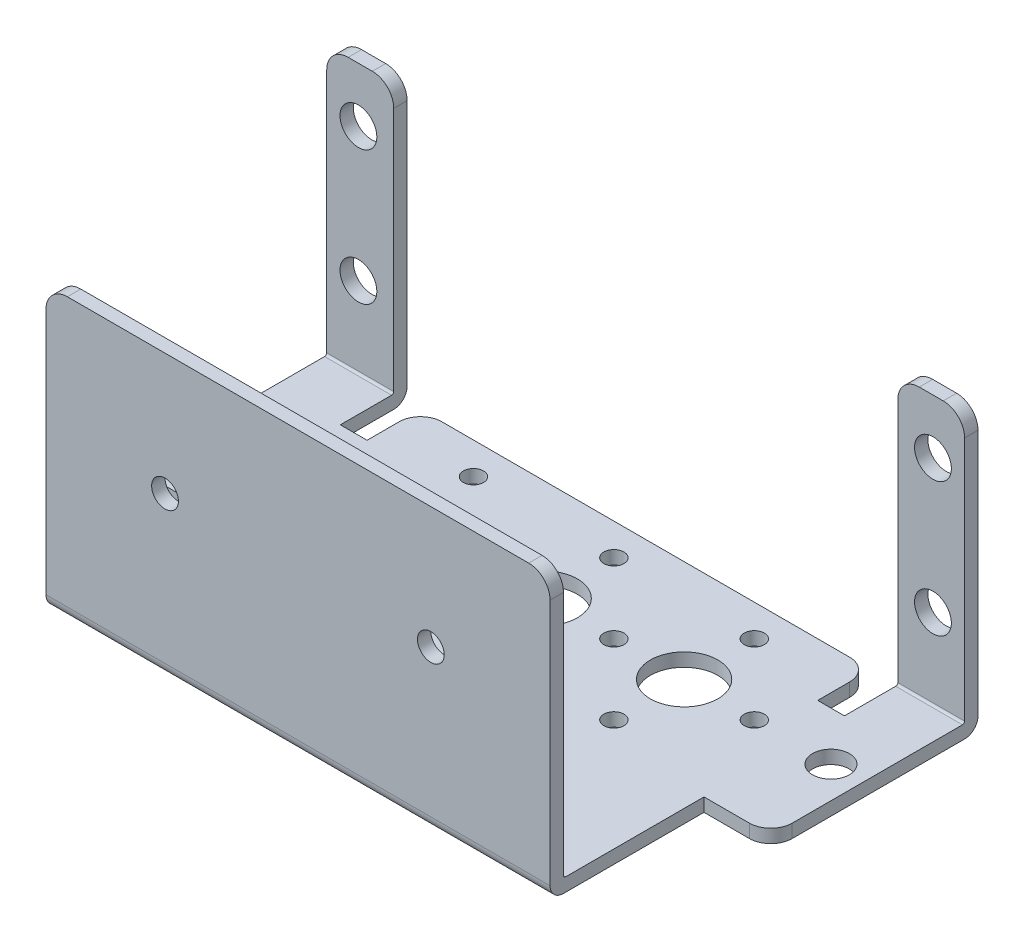
SolidWorks part; units mm, degrees
ref_plane "Front Plane" through (0, 0, 0) normal (0, 0, 1) x (1, 0, 0)
ref_plane "Top Plane" through (0, 0, 0) normal (0, 1, 0) x (1, 0, 0)
ref_plane "Right Plane" through (0, 0, 0) normal (1, 0, 0) x (0, 0, -1)
sketch "Sketch1" plane through (0, 0, 0) normal (1, 0, 0) x (0, 0, -1)
  line L0 (1.5875, 33.4772) -> (1.5875, 1.5875)
  line L1 (1.5875, 0) -> (41.2623, 0)
  line L2 (0, 1.5875) -> (0, 33.4772)
  line L3 (0, 33.4772) -> (1.5875, 33.4772)
  line L4 (42.8498, 1.5875) -> (42.8498, 33.4772)
  line L5 (1.5875, 1.5875) -> (41.2623, 1.5875)
  line L6 (41.2623, 1.5875) -> (41.2623, 33.4772)
  line L7 (41.2623, 33.4772) -> (42.8498, 33.4772)
  arc A0 (1.5875, 0) -> (0, 1.5875) centre (1.5875, 1.5875) cw
  arc A1 (41.2623, 0) -> (42.8498, 1.5875) centre (41.2623, 1.5875) ccw
  point P11 (0, 0)
  point P14 (42.8498, 0)
  dimension "D6" = 1.5875
  dimension "D1" = 33.4772
  dimension "D2" = 42.8498
  dimension "D3" = 1.5875
  dimension "D4" = 1.5875
  dimension "D5" = 1.5875
extrude "Extrude1" add sketch "Sketch1" along normal blind 75.692
sketch "Sketch2" plane through (0, 33.4772, 0) normal (0, 1, 0) x (1, 0, 0)
  line L0 (75.692, 0) -> (0, 0) construction
  line L1 (0, 0) -> (7.9502, 0)
  line L2 (0, 0) -> (0, 18.2626)
  line L3 (0, 18.2626) -> (7.9502, 18.2626)
  line L4 (7.9502, 0) -> (7.9502, 18.2626)
  line L5 (67.7672, 0) -> (75.692, 0)
  line L6 (67.7672, 0) -> (67.7672, 18.2626)
  line L7 (67.7672, 18.2626) -> (75.692, 18.2626)
  line L8 (75.692, 0) -> (75.692, 18.2626)
  line L9 (75.692, 41.2623) -> (75.692, 1.5875) construction
  line L10 (0, 41.2623) -> (0, 1.5875) construction
  dimension "D1" = 7.9502
  dimension "D2" = 18.2626
  dimension "D3" = 67.7672
  dimension "D4" = 18.2626
extrude "Extrude2" cut sketch "Sketch2" against normal up to surface (33.4772 mm away) up to face at (37.846, 0, -21.4249)
sketch "Sketch3" plane through (0, 1.5875, 0) normal (0, 1, 0) x (1, 0, 0)
  line L0 (75.692, 42.8498) -> (0, 42.8498) construction
  line L1 (7.9502, 42.8498) -> (67.7672, 42.8498)
  line L2 (7.9502, 42.8498) -> (7.9502, 41.2623)
  line L3 (7.9502, 41.2623) -> (67.7672, 41.2623)
  line L4 (67.7672, 42.8498) -> (67.7672, 41.2623)
  line L5 (75.692, 41.2623) -> (0, 41.2623) construction
  line L6 (0, 41.2623) -> (0, 18.2626) construction
  dimension "D1" = 7.9502
  dimension "D2" = 67.7672
extrude "Extrude3" cut sketch "Sketch3" along normal up to surface and the other way up to surface up to face at (37.846, 33.4772, -42.056) other way up to face at (37.8524, 0, -19.8438)
sketch "Sketch4" plane through (0, 1.5875, 0) normal (0, 1, 0) x (1, 0, 0)
  line L0 (67.7672, 0) -> (7.9502, 0) construction
  line L1 (7.9502, 41.2623) -> (11.1252, 41.2623)
  line L2 (7.9502, 41.2623) -> (7.9502, 34.925)
  line L3 (7.9502, 34.925) -> (11.1252, 34.925)
  line L4 (11.1252, 41.2623) -> (11.1252, 34.925)
  line L5 (0, 41.2623) -> (0, 18.2626) construction
  line L7 (67.7672, 41.2623) -> (64.5922, 41.2623)
  line L8 (67.7672, 41.2623) -> (67.7672, 34.925)
  line L9 (67.7672, 34.925) -> (64.5922, 34.925)
  line L10 (64.5922, 41.2623) -> (64.5922, 34.925)
  dimension "D1" = 34.925
  dimension "D2" = 11.1252
  dimension "D3" = 34.925
  dimension "D4" = 64.5922
extrude "Extrude4" cut sketch "Sketch4" against normal up to surface (1.5875 mm away) up to face at (37.8536, 0, -24.1275)
sketch "Sketch5" plane through (0, 1.5875, 0) normal (0, 1, 0) x (1, 0, 0)
  line L0 (67.7672, 0) -> (7.9502, 0) construction
  line L1 (0, 41.2623) -> (0, 18.2626) construction
  circle A0 centre (21.1836, 29.1592) radius 4.0005
  circle A1 centre (21.1836, 29.1592) radius 8.3312 construction
  circle A2 centre (21.1836, 37.4904) radius 1.1938
  circle A3 centre (12.8524, 29.1592) radius 1.1938
  circle A4 centre (21.1836, 20.828) radius 1.1938
  circle A5 centre (37.846, 37.4904) radius 1.1938
  circle A6 centre (37.846, 29.1592) radius 8.3312 construction
  circle A7 centre (29.5148, 29.1592) radius 1.1938
  circle A8 centre (37.846, 20.828) radius 1.1938
  circle A9 centre (37.846, 29.1592) radius 4.0005
  circle A10 centre (54.5084, 20.828) radius 1.1938
  circle A11 centre (54.5084, 29.1592) radius 8.3312 construction
  circle A12 centre (54.5084, 29.1592) radius 4.0005
  circle A13 centre (46.1772, 29.1592) radius 1.1938
  circle A14 centre (54.5084, 37.4904) radius 1.1938
  circle A15 centre (62.8396, 29.1592) radius 1.1938
  circle A16 centre (3.7592, 29.1592) radius 2.1844
  circle A17 centre (71.9328, 29.1592) radius 2.1844
  dimension "D1" = 29.1592
  dimension "D3" = 16.6624
  dimension "D4" = 2.3876
  dimension "D5" = 8.001
  dimension "D6" = 3.7592
  dimension "D7" = 4.3688
  dimension "D2" = 21.1836
  dimension "D8" = 71.9328
extrude "Extrude5" cut sketch "Sketch5" against normal up to surface (1.5875 mm away) up to face at (37.8555, 0, -28.9687)
sketch "Sketch6" plane through (0, 0, 0) normal (0, 0, 1) x (1, 0, 0)
  line L0 (67.7672, 0) -> (7.9502, 0) construction
  line L1 (0, 33.4772) -> (0, 1.5875) construction
  circle A0 centre (3.7592, 27.0002) radius 2.1844
  circle A1 centre (3.7592, 11.1252) radius 2.1844
  circle A2 centre (71.9328, 27.0002) radius 2.1844
  circle A3 centre (71.9328, 11.1252) radius 2.1844
  circle A4 centre (22.0726, 19.05) radius 1.5875
  circle A5 centre (53.6194, 19.05) radius 1.5875
  point P16 (0, 17.5323)
  dimension "D1" = 11.1252
  dimension "D5" = 3.175
  dimension "D6" = 3.175
  dimension "D2" = 27.0002
  dimension "D3" = 3.7592
  dimension "D4" = 71.9328
  dimension "D7" = 19.05
  dimension "D8" = 22.0726
  dimension "D9" = 53.6194
extrude "Extrude6" cut sketch "Sketch6" against normal through all
fillet "Fillet1" radius 2.54 7 edges at (11.1252, 0.7937, -41.2623) (75.692, 0.7937, -18.2626) (7.9502, 33.4772, -0.7937) (67.7672, 33.4772, -0.7937) (0, 33.4772, -42.056) (75.692, 33.4772, -42.056) (64.5922, 0.7937, -41.2623)
fillet "Fillet2" radius 0.254 3 edges at (3.9751, 1.5875, -41.2623) (71.7296, 1.5875, -41.2623) (37.8587, 1.5875, -1.5875)
fillet "Fillet3" radius 2.54 1 edges at (0, 0.7937, -18.2626)
fillet "Fillet4" radius 2.54 2 edges at (7.9502, 33.4772, -42.056) (67.7672, 33.4772, -42.056)
ref_axis "Axis1" through (71.9328, 0, -29.1592) along (0, 1, 0)
ref_axis "Axis2" through (3.7592, 0, -29.1592) along (0, 1, 0)
ref_plane "Plane1" through (0, 0, -29.1592) normal (0, 0, -1) x (-1, 0, 0)
ref_axis "Axis3" through (37.846, 0, -20.828) along (0, 1, 0)
ref_axis "Axis4" through (37.846, 0, -37.4904) along (0, 1, 0)
ref_plane "Plane2" through (37.846, 0, 0) normal (1, 0, 0) x (0, 0, -1)
